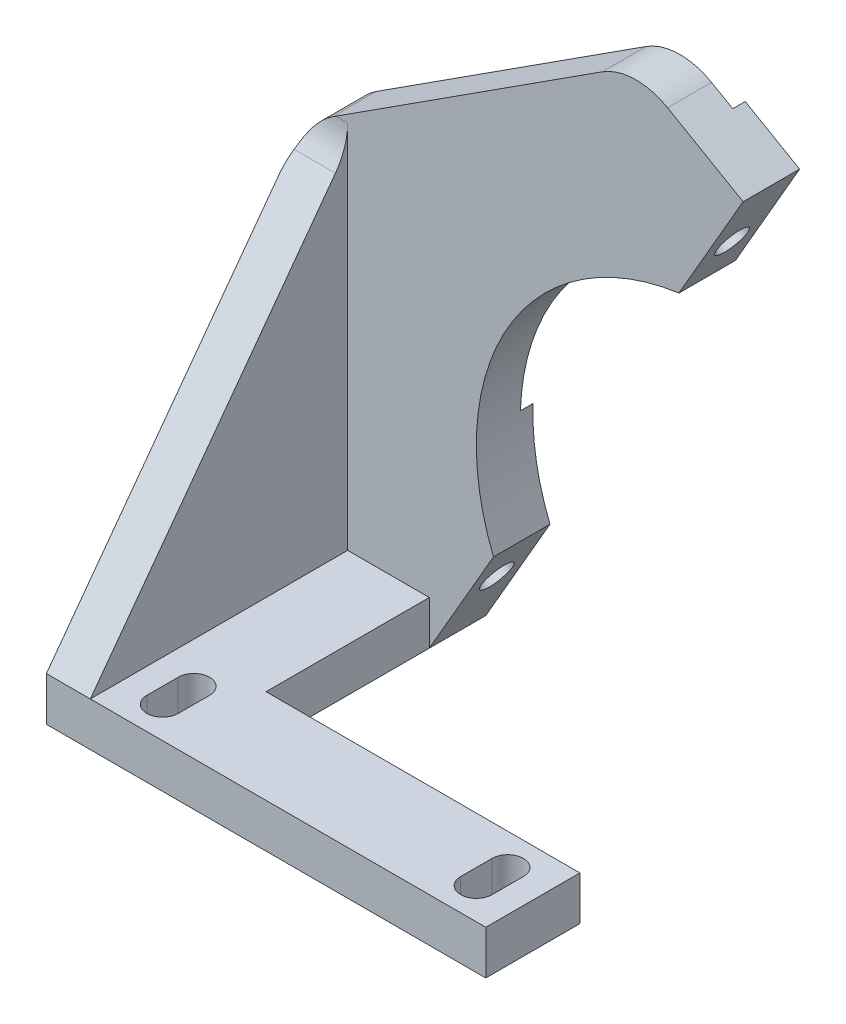
SolidWorks part; units mm, degrees
ref_plane "Front Plane" through (0, 0, 0) normal (0, 0, 1) x (1, 0, 0)
ref_plane "Top Plane" through (0, 0, 0) normal (0, 1, 0) x (1, 0, 0)
ref_plane "Right Plane" through (0, 0, 0) normal (1, 0, 0) x (0, 0, -1)
sketch "Sketch1" plane through (0, 0, 0) normal (0, 0, 1) x (1, 0, 0)
  line L2 (60, 86.6025) -> (42.6795, 96.6025)
  line L3 (55, 31.7543) -> (35, 43.3013) construction
  line L7 (10, 0) -> (60, 86.6025)
  line L9 (10, 0) -> (-10, 0)
  line L10 (-10, 0) -> (-10, 62.6649)
  line L11 (-10, 62.6649) -> (42.6795, 96.6025)
  circle A1 centre (55, 31.7543) radius 37.5
  point P1 (0, 0)
  point P2 (-10, 70.1601)
  point P4 (0, 0)
  point P5 (0, 0)
  dimension "D1" = 120
  dimension "D3" = 100
  dimension "D6" = 75
  dimension "D2" = 20
  dimension "D5" = 55
extrude "Boss-Extrude1" add sketch "Sketch1" against normal blind 7 contours A1 L11 L10 L9 region at (15.2239, 50.3994, 0)
sketch "Sketch5" plane through (0, 0, -7) normal (0, 0, -1) x (-1, 0, 0)
  line L0 (-60, 86.6025) -> (-10, 0)
  line L1 (-10, 0) -> (1.547, 0)
  line L3 (1.547, 0) -> (-51.3397, 91.6025)
  line L4 (-60, 86.6025) -> (-42.6795, 96.6025) construction
  line L5 (-51.3397, 91.6025) -> (-60, 86.6025)
  line L6 (-10, 0) -> (10, 0) construction
  circle A0 centre (-55, 31.7543) radius 37.5
  arc A1 (-20.2274, 17.7144) -> (-49.7726, 68.8881) centre (-55, 31.7543) ccw construction
  point P6 (1.5571, 0)
  arc M4 (-49.7726, 68.8881) -> (-20.2274, 17.7144) centre (-55, 31.7543) cw
  line M5 (-20.2274, 17.7144) -> (-10, 0)
  line M6 (-10, 0) -> (10, 0)
  line M9 (-42.6795, 96.6025) -> (-60, 86.6025)
  line M10 (-60, 86.6025) -> (-49.7726, 68.8881)
  dimension "D1" = 10
extrude "Boss-Extrude3" add sketch "Sketch5" along normal blind 2 contours L3 M4 M9 M10 | L3 M6 M4 M5 region at (48.8381, 78.0295, -7) region at (10.973, 12.7063, -7)
sketch "Sketch6" plane through (7.5, -4.3301, 0) normal (0.866, -0.5, 0) x (0, 0, -1)
  line L0 (4.5, 17.5) -> (4.5, 92.5) construction
  line L1 (0, 55) -> (4.5, 55) construction
  line L2 (0, 84.5452) -> (0, 25.4548) construction
  line L3 (4.5, 92.5) -> (4.5, 105) construction
  line L4 (9, 105) -> (0, 105) construction
  circle A0 centre (4.5, 92.5) radius 3 construction
  circle A1 centre (4.5, 17.5) radius 3 construction
  dimension "D1" = 6
  dimension "D2" = 75
hole_wizard "Tap Drill for M6x1.0 Tap1" positions "Sketch7" profile "Sketch8" hole size "M6x1.0" standard "ANSI Metric"
sketch "Sketch7" plane through (7.5, -4.3301, 0) normal (0.866, -0.5, 0) x (0, 0, -1)
  point P0 (4.5, 92.5)
  point P3 (4.5, 17.5)
sketch "Sketch8" plane through (53.75, 75.7772, -4.5) normal (0, 0, 1) x (0.5, 0.866, 0)
  line L0 (0, 0) -> (0, 9.5022)
  line L1 (0, 9.5022) -> (2.5, 8)
  line L2 (2.5, 8) -> (2.5, 0)
  line L5 (2.5, 0) -> (0, 0)
  line L10 (0, 9.5022) -> (-2.5, 8) construction
  line L11 (0, -6.35) -> (0, 107.95) construction
  dimension "Hole Dia." = 5
  dimension "Hole Depth" = 8
  dimension "Drill Angle" = 118
sketch "Sketch9" plane through (0, 0, 0) normal (0, 1, 0) x (1, 0, 0)
  line L0 (-10, 0) -> (-10, -41)
  line L1 (-10, -41) -> (60, -41)
  line L2 (60, -41) -> (60, -26)
  line L3 (60, -26) -> (10, -26)
  line L4 (10, -26) -> (10, 0)
  line L5 (10, 0) -> (-10, 0)
  line L9 (60, 9) -> (60, 0) construction
  line L11 (10, 9) -> (-1.547, 9) construction
  dimension "D1" = 15
  dimension "D2" = 50
extrude "Boss-Extrude4" add sketch "Sketch9" along normal blind 7
sketch "Sketch10" plane through (-10, 0, 0) normal (-1, 0, 0) x (0, 0, 1)
  line L0 (0, 62.6649) -> (41, 7)
  line L1 (41, 7) -> (0, 7)
  line L2 (0, 7) -> (0, 62.6649)
extrude "Boss-Extrude5" add sketch "Sketch10" against normal blind 7
sketch "Sketch11" plane through (0, 7, 0) normal (0, 1, 0) x (1, 0, 0)
  line L0 (1, -36) -> (1, -31)
  line L1 (6, -36) -> (6, -31)
  line L2 (51, -31) -> (51, -36)
  line L3 (56, -36) -> (56, -31)
  line L4 (3.5, -28.5) -> (3.5, -31) construction
  line L5 (3.5, -31) -> (3.5, -36) construction
  line L6 (3.5, -36) -> (3.5, -38.5) construction
  line L7 (53.5, -31) -> (53.5, -36) construction
  line L8 (3.5, -31) -> (53.5, -31) construction
  line L9 (53.5, -36) -> (3.5, -36) construction
  line L10 (28.5, -41) -> (28.5, -36) construction
  line L11 (-3, -41) -> (60, -41) construction
  line L12 (53.5, -33.5) -> (60, -33.5) construction
  line L13 (60, -41) -> (60, -26) construction
  circle A0 centre (3.5, -31) radius 2.5
  circle A1 centre (3.5, -36) radius 2.5
  circle A2 centre (53.5, -31) radius 2.5
  circle A3 centre (53.5, -36) radius 2.5
  point P22 (51.0687, -33.5)
  dimension "D1" = 5
  dimension "D2" = 10
  dimension "D3" = 50
extrude "Cut-Extrude1" cut sketch "Sketch11" against normal through all contours A0 | A1 L1 A0 | A1 | A1 A0 L0 | A2 | A3 | A3 L3 A2 | A3 A2 L2 region at (3.5, 7, 36) region at (1.5584, 7, 33.5) region at (3.5, 7, 31) region at (5.4416, 7, 33.5) region at (51.5584, 7, 33.5) region at (53.5, 7, 31) region at (53.5, 7, 36) region at (55.4416, 7, 33.5)
fillet "Fillet2" radius 10 3 edges at (-10, 62.6649, -3.5) (42.6795, 96.6025, -3.5) (-6.5, 62.6649, 0)
